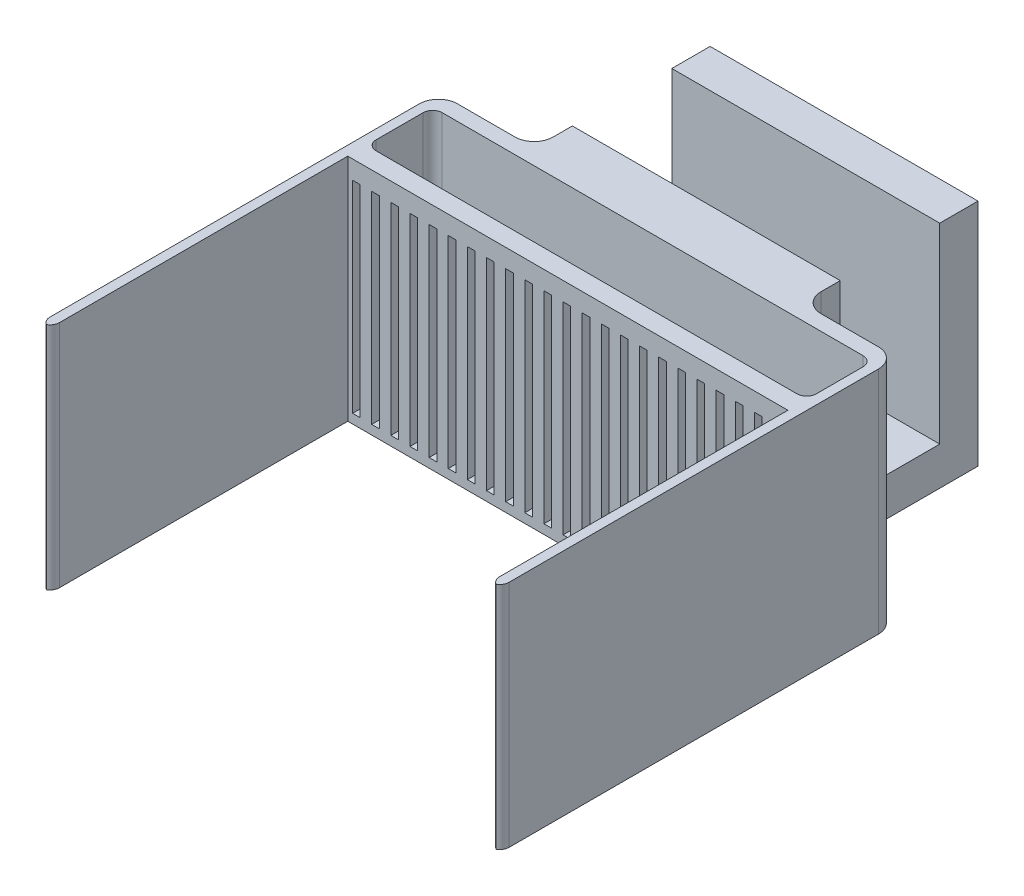
SolidWorks part; units mm, degrees
ref_plane "Plan de face" through (0, 0, 0) normal (0, 0, 1) x (1, 0, 0)
ref_plane "Plan de dessus" through (0, 0, 0) normal (0, 1, 0) x (1, 0, 0)
ref_plane "Plan de droite" through (0, 0, 0) normal (1, 0, 0) x (0, 0, -1)
sketch "Esquisse3" plane through (0, 0, 0) normal (0, 1, 0) x (1, 0, 0)
  line L0 (0, 0) -> (-14, 0)
  line L1 (-14, 0) -> (-14, 5.2)
  line L2 (-14, 5.2) -> (0, 5.2)
  line L3 (0, 5.2) -> (0, 0)
  line L4 (-14, 7.2) -> (0, 7.2)
  line L5 (0, 7.2) -> (0, 5.2)
  line L6 (-14, 0) -> (-14, -2)
  line L7 (-14, -2) -> (0, -2)
  line L8 (0, -2) -> (0, 0)
  line L9 (-14, 7.2) -> (-14, 5.2)
  dimension "D1" = 2
  dimension "D2" = 2
  dimension "D3" = 5.2
  dimension "D4" = 14
extrude "Boss.-Extru.1" add sketch "Esquisse3" along normal blind 10 contours L4 L9 L2 L5 | L7 L8 L0 L6 region at (-7, 0, 1) region at (-7, 0, -6.2)
sketch "Esquisse4" plane through (0, 0, 0) normal (1, 0, 0) x (0, 0, -1)
  line L0 (-2, 0) -> (7.2, 0)
  line L1 (7.2, 0) -> (7.2, -2)
  line L2 (7.2, -2) -> (-2, -2)
  line L3 (-2, -2) -> (-2, 0)
  dimension "D1" = 2
extrude "Boss.-Extru.2" add sketch "Esquisse4" against normal blind 14
sketch "Esquisse5" plane through (0, -2, 0) normal (0, -1, 0) x (1, 0, 0)
  line L0 (-14, 2) -> (-19, 2)
  line L1 (-19, 2) -> (-19, 22.8)
  line L2 (-19, 22.8) -> (-18.5, 22.8)
  line L3 (-18.5, 22.8) -> (-18.5, 2.8)
  line L4 (-18.5, 2.8) -> (4.5, 2.8)
  line L5 (4.5, 2.8) -> (4.5, 22.8)
  line L6 (4.5, 22.8) -> (5, 22.8)
  line L7 (5, 22.8) -> (5, 2)
  line L8 (5, 2) -> (0, 2)
  line L9 (-14, 2) -> (0, 2)
  dimension "D1" = 5
  dimension "D2" = 5
  dimension "D3" = 0.5
  dimension "D4" = 0.5
  dimension "D5" = 20
  dimension "D6" = 20
  dimension "D7" = 23
  dimension "D8" = 20.8
  dimension "D9" = 0.8
extrude "Boss.-Extru.3" add sketch "Esquisse5" against normal blind 12 contours L9 L8 L7 L6 L5 L4 L3 L2 L1 L0
fillet "Congé2" radius 0.5 4 edges at (-19, 4, 22.8) (-18.5, 4, 22.8) (4.5, 4, 22.8) (5, 4, 22.8)
fillet "Congé4" radius 1 1 edges at (-19, 4, 2)
fillet "Congé5" radius 1 1 edges at (5, 4, 2)
fillet "Congé6" radius 1 2 edges at (0, 4, 2) (-14, 4, 2)
sketch "Esquisse6" plane through (0, -2, 0) normal (0, -1, 0) x (-1, 0, 0)
  line L0 (18.5, -6.2558) -> (-4.5, -6.2558)
  line L1 (18.5, -22.3) -> (18.5, -2.8) construction
  line L2 (-4.5, -2.8) -> (-4.5, -22.3) construction
  line L3 (-4.5, -6.2558) -> (-4.5, -7.2357)
  line L4 (-4.5, -7.2357) -> (18.5, -7.2357)
  line L5 (18.5, -7.2357) -> (18.5, -6.2558)
extrude "Boss.-Extru.4" add sketch "Esquisse6" against normal blind 12
fillet "Congé8" radius 0.5 4 edges at (-18.5, 4, 2.8) (4.5, 4, 2.8) (4.5, 4, 6.2558) (-18.5, 4, 6.2558)
sketch "Esquisse7" plane through (0, 0, 7.2357) normal (0, 0, 1) x (1, 0, 0)
  line L0 (-18.5, 10) -> (4.5, 10) construction
  line L1 (4.5, 10) -> (4.5, -2) construction
  line L2 (4.5, -2) -> (-18.5, -2) construction
  line L3 (-18.5, -2) -> (-18.5, 10) construction
  line L4 (-18.25, 10) -> (-18.25, 9.034) construction
  line L5 (-18.25, 9.034) -> (-18.25, -1.5147)
  line L6 (-18.25, -1.5147) -> (-17.85, -1.5147)
  line L7 (-17.85, -1.5147) -> (-17.85, 9.034)
  line L8 (-17.85, 9.034) -> (-18.25, 9.034)
  line L9 (-16.85, 9.034) -> (-17.25, 9.034)
  line L10 (-17.25, 9.034) -> (-17.25, -1.5147)
  line L11 (-17.25, -1.5147) -> (-16.85, -1.5147)
  line L12 (-16.85, -1.5147) -> (-16.85, 9.034)
  line L13 (-15.85, 9.034) -> (-16.25, 9.034)
  line L14 (-16.25, 9.034) -> (-16.25, -1.5147)
  line L15 (-16.25, -1.5147) -> (-15.85, -1.5147)
  line L16 (-15.85, -1.5147) -> (-15.85, 9.034)
  line L17 (-14.85, 9.034) -> (-15.25, 9.034)
  line L18 (-15.25, 9.034) -> (-15.25, -1.5147)
  line L19 (-15.25, -1.5147) -> (-14.85, -1.5147)
  line L20 (-14.85, -1.5147) -> (-14.85, 9.034)
  line L21 (-13.85, 9.034) -> (-14.25, 9.034)
  line L22 (-14.25, 9.034) -> (-14.25, -1.5147)
  line L23 (-14.25, -1.5147) -> (-13.85, -1.5147)
  line L24 (-13.85, -1.5147) -> (-13.85, 9.034)
  line L25 (-12.85, 9.034) -> (-13.25, 9.034)
  line L26 (-13.25, 9.034) -> (-13.25, -1.5147)
  line L27 (-13.25, -1.5147) -> (-12.85, -1.5147)
  line L28 (-12.85, -1.5147) -> (-12.85, 9.034)
  line L29 (-11.85, 9.034) -> (-12.25, 9.034)
  line L30 (-12.25, 9.034) -> (-12.25, -1.5147)
  line L31 (-12.25, -1.5147) -> (-11.85, -1.5147)
  line L32 (-11.85, -1.5147) -> (-11.85, 9.034)
  line L33 (-10.85, 9.034) -> (-11.25, 9.034)
  line L34 (-11.25, 9.034) -> (-11.25, -1.5147)
  line L35 (-11.25, -1.5147) -> (-10.85, -1.5147)
  line L36 (-10.85, -1.5147) -> (-10.85, 9.034)
  line L37 (-9.85, 9.034) -> (-10.25, 9.034)
  line L38 (-10.25, 9.034) -> (-10.25, -1.5147)
  line L39 (-10.25, -1.5147) -> (-9.85, -1.5147)
  line L40 (-9.85, -1.5147) -> (-9.85, 9.034)
  line L41 (-8.85, 9.034) -> (-9.25, 9.034)
  line L42 (-9.25, 9.034) -> (-9.25, -1.5147)
  line L43 (-9.25, -1.5147) -> (-8.85, -1.5147)
  line L44 (-8.85, -1.5147) -> (-8.85, 9.034)
  line L45 (-7.85, 9.034) -> (-8.25, 9.034)
  line L46 (-8.25, 9.034) -> (-8.25, -1.5147)
  line L47 (-8.25, -1.5147) -> (-7.85, -1.5147)
  line L48 (-7.85, -1.5147) -> (-7.85, 9.034)
  line L49 (-6.85, 9.034) -> (-7.25, 9.034)
  line L50 (-7.25, 9.034) -> (-7.25, -1.5147)
  line L51 (-7.25, -1.5147) -> (-6.85, -1.5147)
  line L52 (-6.85, -1.5147) -> (-6.85, 9.034)
  line L53 (-5.85, 9.034) -> (-6.25, 9.034)
  line L54 (-6.25, 9.034) -> (-6.25, -1.5147)
  line L55 (-6.25, -1.5147) -> (-5.85, -1.5147)
  line L56 (-5.85, -1.5147) -> (-5.85, 9.034)
  line L57 (-4.85, 9.034) -> (-5.25, 9.034)
  line L58 (-5.25, 9.034) -> (-5.25, -1.5147)
  line L59 (-5.25, -1.5147) -> (-4.85, -1.5147)
  line L60 (-4.85, -1.5147) -> (-4.85, 9.034)
  line L61 (-3.85, 9.034) -> (-4.25, 9.034)
  line L62 (-4.25, 9.034) -> (-4.25, -1.5147)
  line L63 (-4.25, -1.5147) -> (-3.85, -1.5147)
  line L64 (-3.85, -1.5147) -> (-3.85, 9.034)
  line L65 (-2.85, 9.034) -> (-3.25, 9.034)
  line L66 (-3.25, 9.034) -> (-3.25, -1.5147)
  line L67 (-3.25, -1.5147) -> (-2.85, -1.5147)
  line L68 (-2.85, -1.5147) -> (-2.85, 9.034)
  line L69 (-1.85, 9.034) -> (-2.25, 9.034)
  line L70 (-2.25, 9.034) -> (-2.25, -1.5147)
  line L71 (-2.25, -1.5147) -> (-1.85, -1.5147)
  line L72 (-1.85, -1.5147) -> (-1.85, 9.034)
  line L73 (-0.85, 9.034) -> (-1.25, 9.034)
  line L74 (-1.25, 9.034) -> (-1.25, -1.5147)
  line L75 (-1.25, -1.5147) -> (-0.85, -1.5147)
  line L76 (-0.85, -1.5147) -> (-0.85, 9.034)
  line L77 (0.15, 9.034) -> (-0.25, 9.034)
  line L78 (-0.25, 9.034) -> (-0.25, -1.5147)
  line L79 (-0.25, -1.5147) -> (0.15, -1.5147)
  line L80 (0.15, -1.5147) -> (0.15, 9.034)
  line L81 (1.15, 9.034) -> (0.75, 9.034)
  line L82 (0.75, 9.034) -> (0.75, -1.5147)
  line L83 (0.75, -1.5147) -> (1.15, -1.5147)
  line L84 (1.15, -1.5147) -> (1.15, 9.034)
  line L85 (2.15, 9.034) -> (1.75, 9.034)
  line L86 (1.75, 9.034) -> (1.75, -1.5147)
  line L87 (1.75, -1.5147) -> (2.15, -1.5147)
  line L88 (2.15, -1.5147) -> (2.15, 9.034)
  line L89 (3.15, 9.034) -> (2.75, 9.034)
  line L90 (2.75, 9.034) -> (2.75, -1.5147)
  line L91 (2.75, -1.5147) -> (3.15, -1.5147)
  line L92 (3.15, -1.5147) -> (3.15, 9.034)
  line L93 (4.15, 9.034) -> (3.75, 9.034)
  line L94 (3.75, 9.034) -> (3.75, -1.5147)
  line L95 (3.75, -1.5147) -> (4.15, -1.5147)
  line L96 (4.15, -1.5147) -> (4.15, 9.034)
  dimension "D1" = 0.25
  dimension "D2" = 0.4
  dimension "D3" = 23
extrude "Enlèv. mat.-Extru.1" cut sketch "Esquisse7" against normal blind 1.5
